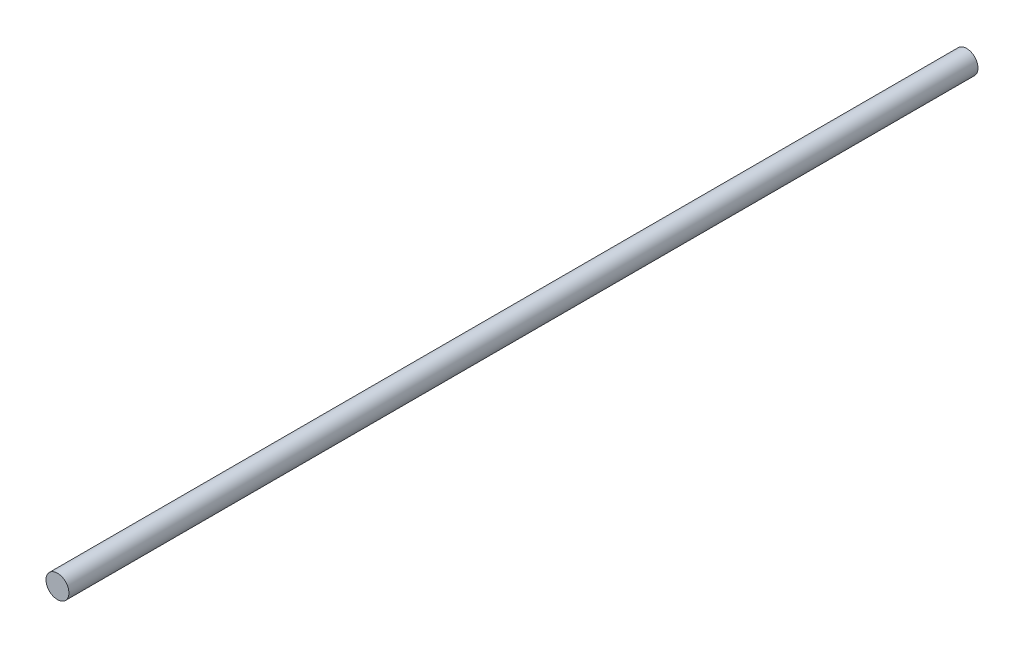
SolidWorks part; units mm, degrees
ref_plane "Plano frontal" through (0, 0, 0) normal (0, 0, 1) x (1, 0, 0)
ref_plane "Plano superior" through (0, 0, 0) normal (0, 1, 0) x (1, 0, 0)
ref_plane "Plano direito" through (0, 0, 0) normal (1, 0, 0) x (0, 0, -1)
sketch "Esboço1" plane through (0, 0, 0) normal (0, 0, 1) x (1, 0, 0)
  circle A0 centre (0, 0) radius 4
  dimension "D1" = 8
extrude "Ressalto-extrusão1" add sketch "Esboço1" along normal mid plane 317
ref_axis "Eixo1" through (0, 0, 158.5) along (0, 0, -1)
